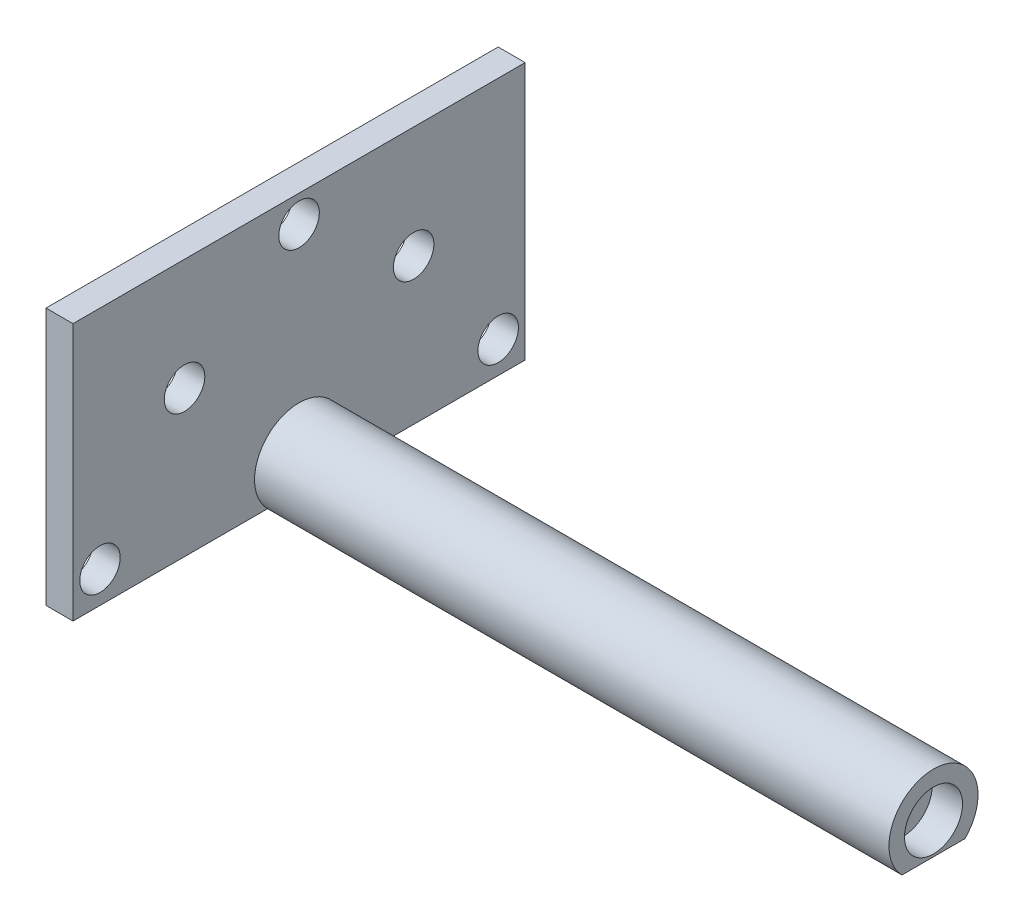
SolidWorks part; units mm, degrees
ref_plane "Front Plane" through (0, 0, 0) normal (0, 0, 1) x (1, 0, 0)
ref_plane "Top Plane" through (0, 0, 0) normal (0, 1, 0) x (1, 0, 0)
ref_plane "Right Plane" through (0, 0, 0) normal (1, 0, 0) x (0, 0, -1)
sketch "Sketch1" plane through (0, 0, 0) normal (1, 0, 0) x (0, 0, -1)
  line L0 (-8.4853, 8.4853) -> (-14.75, 0) construction
  line L1 (-8.4853, 8.4853) -> (0, 14.75) construction
  line L3 (-16.75, -2.3335) -> (16.75, -2.3335)
  line L4 (-16.75, -2.3335) -> (-16.75, 16.75)
  line L5 (-16.75, 16.75) -> (16.75, 16.75)
  line L6 (16.75, -2.3335) -> (16.75, 16.75)
  line L7 (-2.3335, -2.3335) -> (2.3335, -2.3335)
  line L8 (-2.3335, -2.3335) -> (-2.3335, 2.3335)
  line L9 (-2.3335, 2.3335) -> (2.3335, 2.3335)
  line L10 (2.3335, -2.3335) -> (2.3335, 2.3335)
  circle A0 centre (0, 0) radius 14.75 construction
  circle A1 centre (0, 14.75) radius 1.5
  circle A2 centre (0, 0) radius 14.75 construction
  circle A3 centre (14.75, 0) radius 1.5
  circle A4 centre (0, 0) radius 14.75 construction
  circle A5 centre (0, -14.75) radius 1.5 construction
  circle A6 centre (0, 0) radius 14.75 construction
  circle A7 centre (-14.75, 0) radius 1.5
  circle A8 centre (0, 0) radius 12 construction
  circle A9 centre (-8.4853, 8.4853) radius 1.5
  circle A10 centre (8.4853, 8.4853) radius 1.5
  circle A11 centre (8.4853, -8.4853) radius 1.5 construction
  circle A12 centre (-8.4853, -8.4853) radius 1.5 construction
  circle A13 centre (0, 0) radius 3.3
  point P16 (0, 0)
  point P27 (0, 0)
  point P34 (0, 0)
  point P35 (0, 0)
  dimension "D1" = 4
  dimension "D2" = 4
  dimension "D3" = 2
  dimension "D6" = 3
  dimension "D7" = 6.6
  dimension "D8" = 29.5
  dimension "D9" = 24
  dimension "D4" = 2
  dimension "D5" = 2
extrude "Boss-Extrude1" add sketch "Sketch1" along normal blind 2 contours L3 L6 L5 L4 A10 A9 A7 A3 A1 | L3 L10 L9 L8 | L8 A13 | L9 A13 | L10 A13 region at (0, 7.6382, 0) region at (0, 0, 0) region at (0, 0, 2.7254) region at (0, 0, -2.7254) region at (0, 2.7254, 0)
extrude "Boss-Extrude2" add sketch "Sketch1<3>" along normal blind 49 contours L3 L10 L9 L8 | L8 A13 | L9 A13 | L10 A13 region at (0, 0, 0) region at (0, 0, 2.7254) region at (0, 0, -2.7254) region at (0, 2.7254, 0)
sketch "Sketch1<3>" plane through (0, 0, 0) normal (1, 0, 0) x (0, 0, -1) same geometry as "Sketch1"
sketch "Sketch3" plane through (49, 0, 0) normal (1, 0, 0) x (0, 0, -1)
  circle A1 centre (0, 0) radius 2.15
extrude "Cut-Extrude1" cut sketch "Sketch3" against normal blind 2.25 contours A1
